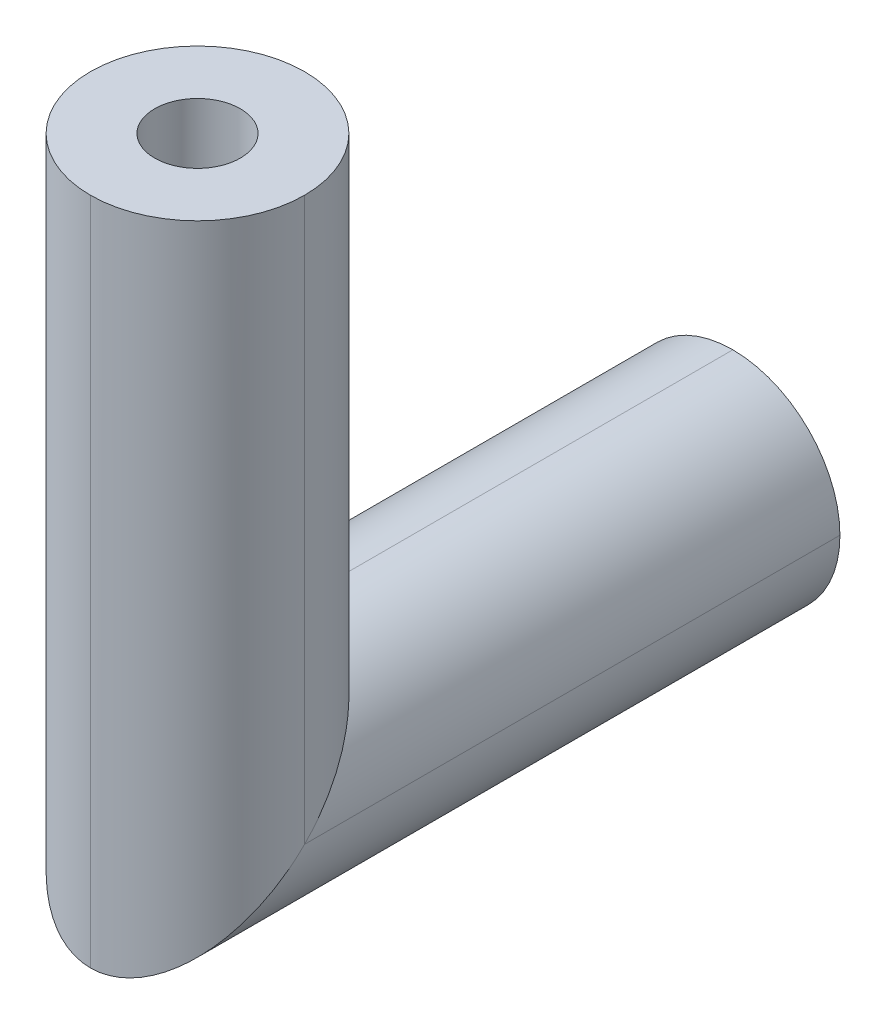
SolidWorks part; units mm, degrees
ref_plane "Plan de face" through (0, 0, 0) normal (0, 0, 1) x (1, 0, 0)
ref_plane "Plan de dessus" through (0, 0, 0) normal (0, 1, 0) x (1, 0, 0)
ref_plane "Plan de droite" through (0, 0, 0) normal (1, 0, 0) x (0, 0, -1)
sketch "Esquisse4" plane through (0, 0, 0) normal (1, 0, 0) x (0, 0, -1)
  line L0 (4, 4) -> (12, 4)
  line L1 (0, 0) -> (4, 0)
  line L2 (0, 0) -> (0, 12.5)
  line L3 (0, 12.5) -> (4, 12.5)
  line L4 (4, 0) -> (4, 12.5)
  line L5 (12, 4) -> (12, 0)
  line L6 (12, 0) -> (4, 0)
  line L7 (4, 4) -> (4, 0) construction
  dimension "D1" = 12.5
  dimension "D2" = 4
  dimension "D3" = 90
  dimension "D5" = 4
  dimension "D6" = 8
extrude "Boss.-Extru.2" add sketch "Esquisse4" along normal blind 4 contours L0 L7 L6 L5 | L7 L4 L6 | L1 L4 L3 L2 region at (0, 2, -8) region at (0, 6.25, -2)
sketch "Esquisse10" plane through (0, 12.5, 0) normal (0, 1, 0) x (1, 0, 0)
  line L0 (0, 2) -> (4, 2) construction
  line L1 (0, 0) -> (0, 4) construction
  line L2 (4, 0) -> (4, 4) construction
  circle A0 centre (2, 2) radius 0.8
  dimension "D1" = 1.6
extrude "Enlèv. mat.-Extru.3" cut sketch "Esquisse10" against normal blind 8
sketch "Esquisse11" plane through (0, 0, 0) normal (0, -1, 0) x (1, 0, 0)
  line L0 (0, 0) -> (4, -4) construction
  line L1 (4, -12) -> (4, 0) construction
  line L2 (4, 0) -> (4, -4) construction
  line L3 (4, 0) -> (0, 0) construction
  circle A0 centre (2, -2) radius 0.8
  dimension "D1" = 1.6
extrude "Enlèv. mat.-Extru.4" cut sketch "Esquisse11" against normal blind 4
sketch "Esquisse6" plane through (0, 12.5, 0) normal (0, 1, 0) x (1, 0, 0)
  line L0 (0, 2) -> (4, 2) construction
  line L1 (0, 0) -> (0, 4) construction
  line L2 (4, 0) -> (4, 4) construction
  circle A0 centre (2, 2) radius 0.8
  dimension "D1" = 1.6
sketch "Esquisse7" plane through (0, 0, -12) normal (0, 0, -1) x (1, 0, 0)
  line L0 (0, -2) -> (4, -2) construction
  line L1 (0, -4) -> (0, 0) construction
  line L2 (4, -4) -> (4, 0) construction
  circle A0 centre (2, -2) radius 0.8
  dimension "D1" = 1.6
extrude "Enlèv. mat.-Extru.2" cut sketch "Esquisse7" against normal blind 8
fillet "Congé4" radius 2 8 edges at (4, 0, -6) (0, 0, -6) (4, 8.25, -4) (0, 8.25, -4) (4, 4, -8) (0, 4, -8) (4, 6.25, 0) (0, 6.25, 0)
